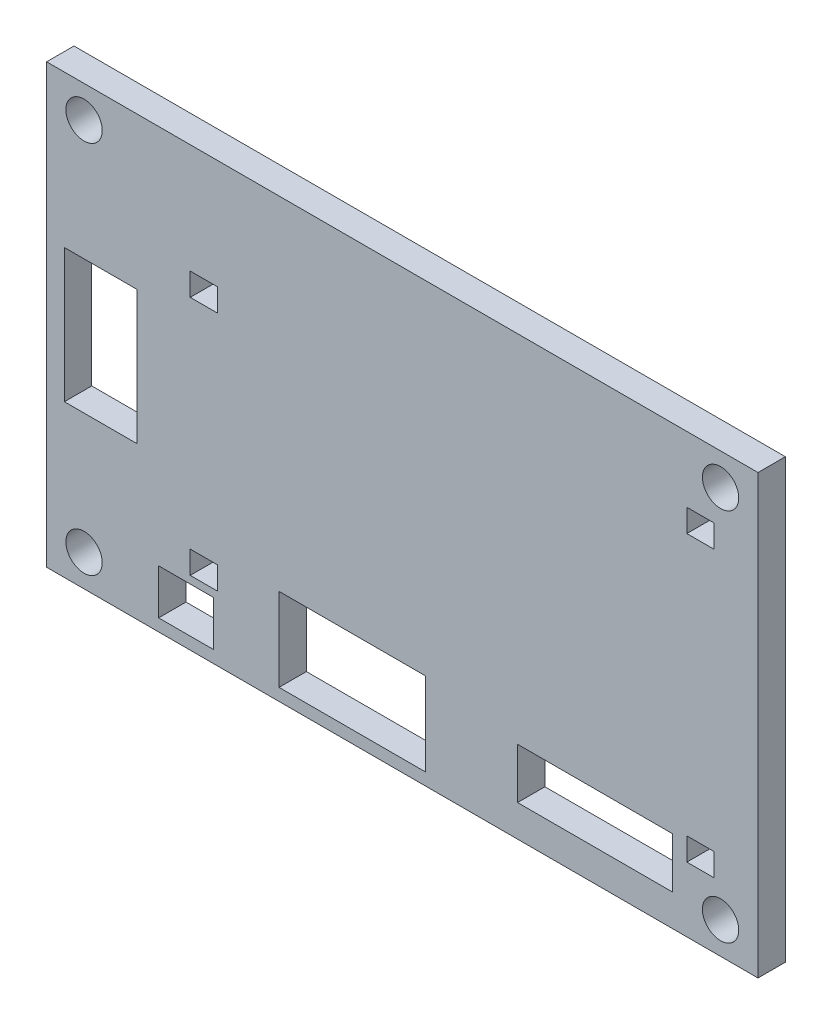
SolidWorks part; units mm, degrees
material "Beech"
ref_plane "Front Plane" through (0, 0, 0) normal (0, 0, 1) x (1, 0, 0)
ref_plane "Top Plane" through (0, 0, 0) normal (0, 1, 0) x (1, 0, 0)
ref_plane "Right Plane" through (0, 0, 0) normal (1, 0, 0) x (0, 0, -1)
sketch "Sketch1" plane through (0, 0, 0) normal (0, 0, 1) x (1, 0, 0)
  line L0 (-20.6375, 0) -> (20.6375, 0)
  line L44 (0, 14.605) -> (0, 24.13) construction
  line L46 (-20.6375, 0) -> (-20.6375, 25.4)
  line L47 (-20.6375, 25.4) -> (20.6375, 25.4)
  line L48 (20.6375, 0) -> (20.6375, 25.4)
  line L49 (-20.6375, 12.7) -> (20.6375, 12.7) construction
  circle A2 centre (-18.4658, 23.5585) radius 1.0541
  circle A3 centre (-18.4658, 1.8415) radius 1.0541
  circle A4 centre (18.4658, 1.8415) radius 1.0541
  circle A5 centre (18.4658, 23.5585) radius 1.0541
  point P0 (0, 0)
  point P56 (0, 12.7)
  point P60 (0, 25.4)
  dimension "D14" = 12.7
  dimension "D4" = 2.1082
  dimension "D3" = 25.4
  dimension "D12" = 41.275
  dimension "D5" = 2.1717
  dimension "D6" = 1.8415
extrude "Boss-Extrude1" add sketch "Sketch1" along normal blind 1.5875 contours L48 L47 L46 region at (0, 12.7, 0)
fillet "Fillet7" [suppressed] radius 15.24
sketch "Sketch2" plane through (0, 0, 1.5875) normal (0, 0, 1) x (1, 0, 0)
  line L4 (-20.6375, 0) -> (-20.6375, 25.4) construction
  line L5 (-20.6375, 25.4) -> (20.6375, 25.4) construction
  line L6 (-20.6375, 0) -> (20.6375, 0) construction
  line L7 (20.6375, 0) -> (20.6375, 25.4) construction
  line L8 (6.6858, 1.8395) -> (15.6858, 1.8395)
  line L9 (6.6858, 4.7695) -> (6.6858, 1.8395)
  line L10 (15.6858, 4.7695) -> (6.6858, 4.7695)
  line L11 (15.6858, 1.8395) -> (15.6858, 4.7695)
  line L12 (-10.7188, 5.08) -> (-10.7188, 3.7592) construction
  line L13 (-10.7188, 3.7592) -> (-12.3063, 3.7592) construction
  line L14 (-12.3063, 3.7592) -> (-12.3063, 5.08) construction
  line L15 (-12.3063, 5.08) -> (-10.7188, 5.08) construction
  line L16 (1.3552, 5.5335) -> (-7.1538, 5.5335)
  line L17 (1.3552, 0.7075) -> (1.3552, 5.5335)
  line L18 (-7.1538, 0.7075) -> (1.3552, 0.7075)
  line L19 (-7.1538, 5.5335) -> (-7.1538, 0.7075)
  line L20 (18.0975, 5.08) -> (18.0975, 3.7592) construction
  line L21 (18.0975, 3.7592) -> (16.51, 3.7592) construction
  line L22 (16.51, 3.7592) -> (16.51, 5.08) construction
  line L23 (16.51, 5.08) -> (18.0975, 5.08) construction
  line L24 (-10.9638, 3.3237) -> (-14.1388, 3.3237)
  line L25 (-10.9638, 0.7075) -> (-10.9638, 3.3237)
  line L26 (-14.1388, 0.7075) -> (-10.9638, 0.7075)
  line L27 (-14.1388, 3.3237) -> (-14.1388, 0.7075)
  line L28 (18.0975, 21.59) -> (18.0975, 20.2692) construction
  line L29 (18.0975, 20.2692) -> (16.51, 20.2692) construction
  line L30 (16.51, 20.2692) -> (16.51, 21.59) construction
  line L31 (16.51, 21.59) -> (18.0975, 21.59) construction
  line L32 (-19.6078, 8.834) -> (-15.3878, 8.834)
  line L33 (-19.6078, 16.584) -> (-19.6078, 8.834)
  line L34 (-15.3878, 16.584) -> (-19.6078, 16.584)
  line L35 (-15.3878, 8.834) -> (-15.3878, 16.584)
  line L48 (-10.7188, 5.08) -> (-10.7188, 3.7592)
  line L49 (-10.7188, 3.7592) -> (-12.3063, 3.7592)
  line L50 (-12.3063, 3.7592) -> (-12.3063, 5.08)
  line L51 (-12.3063, 5.08) -> (-10.7188, 5.08)
  line L52 (18.0975, 5.08) -> (18.0975, 3.7592)
  line L53 (18.0975, 3.7592) -> (16.51, 3.7592)
  line L54 (16.51, 3.7592) -> (16.51, 5.08)
  line L55 (16.51, 5.08) -> (18.0975, 5.08)
  line L56 (18.0975, 21.59) -> (18.0975, 20.2692)
  line L57 (18.0975, 20.2692) -> (16.51, 20.2692)
  line L58 (16.51, 20.2692) -> (16.51, 21.59)
  line L59 (16.51, 21.59) -> (18.0975, 21.59)
  line L64 (-10.7188, 17.7292) -> (-10.7188, 19.05)
  line L65 (-12.3063, 17.7292) -> (-10.7188, 17.7292)
  line L66 (-12.3063, 19.05) -> (-12.3063, 17.7292)
  line L67 (-10.7188, 19.05) -> (-12.3063, 19.05)
  line L68 (-10.7188, 17.7292) -> (-10.7188, 19.05)
  line L69 (-12.3063, 17.7292) -> (-10.7188, 17.7292)
  line L70 (-12.3063, 19.05) -> (-12.3063, 17.7292)
  line L71 (-10.7188, 19.05) -> (-12.3063, 19.05)
  dimension "D1" = 4.22
  dimension "D2" = 7.75
  dimension "D3" = 1.0297
  dimension "D4" = 8.816
  dimension "D5" = 3.175
  dimension "D6" = 2.6162
  dimension "D7" = 0.7075
  dimension "D8" = 6.4987
  dimension "D9" = 8.509
  dimension "D10" = 4.826
  dimension "D11" = 0.7075
  dimension "D12" = 19.2823
  dimension "D13" = 9
  dimension "D14" = 2.93
  dimension "D15" = 1.8395
  dimension "D16" = 4.9517
  dimension "D17" = 0
extrude "Cut-Extrude1" cut sketch "Sketch2" against normal up to surface (1.5875 mm away) up to face at (-17.4117, 1.8415, 0)
move or copy body "Body-Move/Copy1" [suppressed] bodies to move or copy 105
